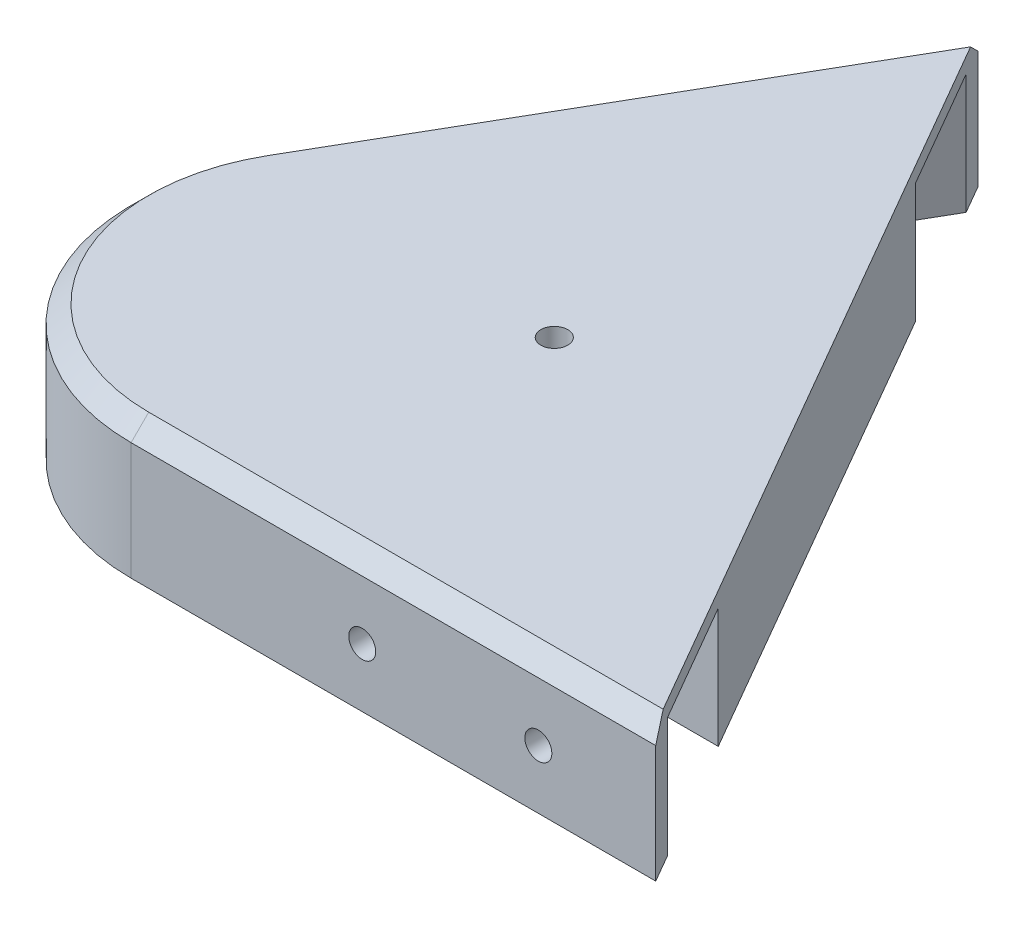
SolidWorks part; units mm, degrees
ref_plane "Front Plane" through (0, 0, 0) normal (0, 0, 1) x (1, 0, 0)
ref_plane "Top Plane" through (0, 0, 0) normal (0, 1, 0) x (1, 0, 0)
ref_plane "Right Plane" through (0, 0, 0) normal (1, 0, 0) x (0, 0, -1)
sketch "Sketch1" plane through (0, 0, 0) normal (0, 1, 0) x (1, 0, 0)
  line L0 (0, 0) -> (150, 0)
  line L1 (0, 0) -> (75, 129.9038)
  line L2 (75, 129.9038) -> (150, 0)
  dimension "D1" = 60
  dimension "D2" = 150
  dimension "D3" = 60
extrude "Boss-Extrude1" add sketch "Sketch1" along normal blind 23
sketch "Sketch2" plane through (0, 0, 0) normal (0, 1, 0) x (1, 0, 0)
  line L0 (0, 0) -> (150, 0) construction
  line L1 (74, 5) -> (174, 5) construction
  line L2 (74, 5) -> (74, 25) construction
  line L3 (74, 25) -> (174, 25) construction
  line L4 (174, 5) -> (174, 25) construction
  line L5 (41.3301, 61.5859) -> (91.3301, 148.1884) construction
  line L6 (91.3301, 148.1884) -> (108.6506, 138.1884) construction
  line L7 (108.6506, 138.1884) -> (58.6506, 51.5859) construction
  line L8 (58.6506, 51.5859) -> (41.3301, 61.5859) construction
  line L9 (75, 129.9038) -> (0, 0) construction
  line L10 (108.9238, 138.2616) -> (58.7238, 51.3127)
  line L11 (58.7238, 51.3127) -> (41.0569, 61.5127)
  line L12 (41.0569, 61.5127) -> (91.2569, 148.4616)
  line L13 (91.2569, 148.4616) -> (108.9238, 138.2616)
  line L14 (73.8, 25.2) -> (174.2, 25.2)
  line L15 (174.2, 4.8) -> (174.2, 25.2)
  line L16 (73.8, 4.8) -> (174.2, 4.8)
  line L17 (73.8, 4.8) -> (73.8, 25.2)
  dimension "D1" = 20
  dimension "D2" = 5
  dimension "D3" = 74
  dimension "D4" = 20
  dimension "D5" = 74
  dimension "D6" = 5
  dimension "D7" = 100
  dimension "D8" = 100
  dimension "D9" = 0.2
  dimension "D10" = 0.2
extrude "Cut-Extrude2" cut sketch "Sketch2" along normal blind 20.4
sketch "Sketch4" plane through (0, 0, 0) normal (0, 1, 0) x (1, 0, 0)
  line L4 (135.4508, 25.2) -> (89.5492, 104.7038) construction
  line L6 (0, 0) -> (52.9457, 91.7047) construction
  line L7 (71.1846, 26.4561) -> (50.3755, 17.6234) construction
  line L8 (71.1846, 26.4561) -> (59.8815, 46.0336) construction
  line L9 (59.8815, 46.0336) -> (42.561, 36.0336) construction
  line L10 (50.3755, 17.6234) -> (42.561, 36.0336) construction
  line L11 (71.1846, 26.4561) -> (42.561, 36.0336) construction
  line L12 (59.8815, 46.0336) -> (50.3755, 17.6234) construction
  line L13 (59.9548, 46.3068) -> (42.3078, 36.1183)
  line L14 (75, 129.9038) -> (0, 0) construction
  line L15 (0, 0) -> (130.8784, 0) construction
  line L16 (0, 0) -> (150, 0) construction
  line L17 (50.2696, 17.3612) -> (42.3078, 36.1183)
  line L18 (71.4708, 26.3604) -> (50.2696, 17.3612)
  line L19 (71.4708, 26.3604) -> (59.9548, 46.3068)
  point P0 (55.1285, 31.8285)
  dimension "D1" = 20
  dimension "D2" = 20
  dimension "D3" = 53.2569
  dimension "D4" = 0.2
extrude "Cut-Extrude3" cut sketch "Sketch4" along normal blind 20
sketch "Sketch5" plane through (0, 0, 0) normal (0, -1, 0) x (1, 0, 0)
  line L0 (69.3641, -52.1717) -> (70.0962, -54.9038) construction
  line L1 (70.0962, -54.9038) -> (76.5913, -58.6538) construction
  line L2 (76.5913, -58.6538) -> (75.0913, -61.2519) construction
  line L3 (75.0913, -61.2519) -> (77.6894, -62.7519) construction
  line L4 (77.6894, -62.7519) -> (79.1894, -60.1538) construction
  line L5 (79.1894, -60.1538) -> (85.6846, -63.9038) construction
  line L6 (85.6846, -63.9038) -> (88.4167, -63.1717) construction
  line L7 (88.4167, -63.1717) -> (98.9167, -44.9852) construction
  line L8 (98.9167, -44.9852) -> (98.1846, -42.2532) construction
  line L9 (98.1846, -42.2532) -> (91.6894, -38.5032) construction
  line L10 (91.6894, -38.5032) -> (93.1894, -35.9051) construction
  line L11 (93.1894, -35.9051) -> (90.5913, -34.4051) construction
  line L12 (90.5913, -34.4051) -> (89.0913, -37.0032) construction
  line L13 (89.0913, -37.0032) -> (82.5962, -33.2532) construction
  line L14 (82.5962, -33.2532) -> (79.8641, -33.9852) construction
  line L15 (79.8641, -33.9852) -> (69.3641, -52.1717) construction
  line L16 (68.9349, -52.1152) -> (69.7527, -55.1674)
  line L17 (69.7527, -55.1674) -> (76.0449, -58.8002)
  line L18 (76.0449, -58.8002) -> (74.5449, -61.3983)
  line L19 (74.5449, -61.3983) -> (77.8358, -63.2983)
  line L20 (77.8358, -63.2983) -> (79.3358, -60.7002)
  line L21 (79.3358, -60.7002) -> (85.6281, -64.333)
  line L22 (85.6281, -64.333) -> (88.6802, -63.5152)
  line L23 (88.6802, -63.5152) -> (99.3459, -45.0417)
  line L24 (99.3459, -45.0417) -> (98.5281, -41.9896)
  line L25 (98.5281, -41.9896) -> (92.2358, -38.3567)
  line L26 (92.2358, -38.3567) -> (93.7358, -35.7587)
  line L27 (93.7358, -35.7587) -> (90.4449, -33.8587)
  line L28 (90.4449, -33.8587) -> (88.9449, -36.4567)
  line L29 (88.9449, -36.4567) -> (82.6527, -32.8239)
  line L30 (82.6527, -32.8239) -> (79.6005, -33.6417)
  line L31 (79.6005, -33.6417) -> (68.9349, -52.1152)
  dimension "D1" = 0.4
extrude "Cut-Extrude4" cut sketch "Sketch5" against normal offset from surface (18 mm away) 5 up to face at (75, 23, -43.3013)
sketch "Sketch6" plane through (0, 18, 0) normal (0, -1, 0) x (1, 0, 0)
  circle A0 centre (84.1404, -48.5785) radius 2.3
  dimension "D1" = 4.6
extrude "Cut-Extrude5" cut sketch "Sketch6" against normal through all
sketch "Sketch7" plane through (0, 0, 0) normal (-0.866, 0, -0.5) x (-0.5, 0, 0.866)
  line L0 (-150, 0) -> (0, 0) construction
  line L1 (-150, 23) -> (-150, 0) construction
  circle A0 centre (-130, 10) radius 2.3
  circle A1 centre (-100, 10) radius 2.3
  dimension "D1" = 4.6
  dimension "D2" = 10
  dimension "D3" = 20
  dimension "D4" = 30
extrude "Cut-Extrude6" cut sketch "Sketch7" against normal blind 10
sketch "Sketch8" plane through (0, 0, 0) normal (0, 0, 1) x (1, 0, 0)
  line L0 (150, 23) -> (150, 0) construction
  line L1 (0, 0) -> (150, 0) construction
  circle A0 centre (130, 10) radius 2.3
  circle A1 centre (100, 10) radius 2.3
  dimension "D1" = 4.6
  dimension "D2" = 20
  dimension "D3" = 10
  dimension "D4" = 30
extrude "Cut-Extrude7" cut sketch "Sketch8" against normal blind 10
sketch "Sketch9" plane through (48.8393, 0, -20.7306) normal (0.9205, 0, -0.3907) x (-0.3907, 0, -0.9205)
  line L2 (0, 20) -> (0, 0) construction
  line L3 (10.2, 10) -> (-10.2, 10) construction
  line L4 (-3.6605, 20) -> (-3.6605, 0) construction
  line L5 (16.7165, 20) -> (-3.6605, 20) construction
  line L6 (16.7165, 20) -> (16.7165, 0) construction
  line L7 (16.7165, 0) -> (-3.6605, 0) construction
  circle A0 centre (0, 10) radius 2.3
  dimension "D3" = 4.6
extrude "Cut-Extrude8" cut sketch "Sketch9" against normal through all
ref_plane "Plane1" through (45.1573, 0, -19.1677) normal (0.9205, 0, -0.3907) x (-0.3907, 0, -0.9205)
sketch "Sketch10" plane through (45.1573, 0, -19.1677) normal (0.9205, 0, -0.3907) x (-0.3907, 0, -0.9205)
  circle A0 centre (0, 10) radius 4.5
  dimension "D1" = 9
extrude "Cut-Extrude9" cut sketch "Sketch10" against normal through all
sketch "Sketch20" plane through (0, 0, 0) normal (0, -1, 0) x (1, 0, 0)
  line L4 (51.0487, -17.695) -> (40.8487, -35.3619)
  line L5 (40.8487, -35.3619) -> (58.5156, -45.5619)
  line L6 (58.5156, -45.5619) -> (68.7156, -27.895)
  line L7 (68.7156, -27.895) -> (51.0487, -17.695)
  line L8 (72.8137, -26.7969) -> (49.9506, -13.5969)
  line L9 (49.9506, -13.5969) -> (36.7506, -36.46)
  line L10 (36.7506, -36.46) -> (59.6137, -49.66)
  line L11 (59.6137, -49.66) -> (72.8137, -26.7969)
  dimension "D1" = 3
  dimension "D2" = 3
  dimension "D3" = 3
  dimension "D4" = 3
extrude "Boss-Extrude5" add sketch "Sketch20" along normal blind 5
chamfer "Chamfer2" distance 5 angle 45 4 edges at (61.3821, 0, -20.1969) (48.1821, 0, -43.06) (43.3506, 0, -25.0285) (66.2137, 0, -38.2285)
fillet "Fillet3" radius 35 1 edges at (0, 18.75, 0)
chamfer "Chamfer1" distance 3 angle 45 3 edges at (52.6554, 23, -91.2019) (105.3109, 23, 0) (30.3109, 23, -17.5)
sketch "Sketch21" plane through (0, 0, 0) normal (0, -1, 0) x (1, 0, 0)
  line L0 (130.2546, -28.2) -> (112.5336, -28.2)
  line L1 (112.5336, -28.2) -> (80.6887, -83.3569)
  line L2 (80.6887, -83.3569) -> (89.5492, -98.7038)
  line L3 (89.5492, -98.7038) -> (130.2546, -28.2)
  line L4 (135.4508, -25.2) -> (89.5492, -104.7038) construction
  line L5 (135.4508, -25.2) -> (73.8, -25.2) construction
  line L6 (88.6802, -63.5152) -> (99.3459, -45.0417) construction
  line L7 (58.7238, -51.3127) -> (89.5492, -104.7038) construction
  line L8 (61.5784, -56.2569) -> (89.5492, -104.7038) construction
  dimension "D1" = 3
  dimension "D2" = 3
  dimension "D3" = 3
  dimension "D4" = 3
extrude "Cut-Extrude10" cut sketch "Sketch21" against normal offset from surface (20 mm away) 3 up to face at (84.1404, 23, -50.8785)
